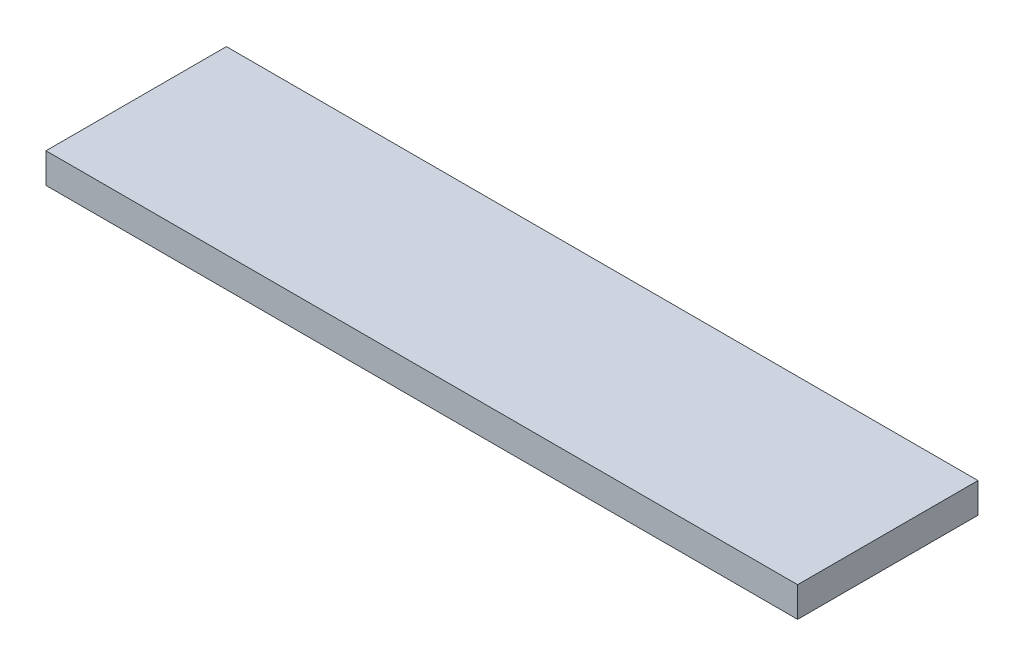
SolidWorks part; units mm, degrees
material "Natural Rubber"
ref_plane "Front" through (0, 0, 0) normal (0, 0, 1) x (1, 0, 0)
ref_plane "Top" through (0, 0, 0) normal (0, 1, 0) x (1, 0, 0)
ref_plane "Right" through (0, 0, 0) normal (1, 0, 0) x (0, 0, -1)
sketch "Sketch1" plane through (0, 0, 0) normal (0, 1, 0) x (1, 0, 0)
  line L1 (-1447.8, 825.5) -> (1447.8, 825.5)
  line L2 (-1447.8, 825.5) -> (-1447.8, -825.5)
  line L3 (-1447.8, -825.5) -> (1447.8, -825.5)
  line L4 (1447.8, 825.5) -> (1447.8, -825.5)
  line L5 (-1447.8, 825.5) -> (1447.8, -825.5) construction
  line L6 (-1447.8, -825.5) -> (1447.8, 825.5) construction
  point P0 (0, 0)
  dimension "D1" = 2895.6
  dimension "D2" = 1651
extrude "Boss-Extrude1" [suppressed] add sketch "Sketch1" along normal blind 1473.2
sketch "Sketch2" [suppressed] plane through (0, 0, 0) normal (0, -1, 0) x (1, 0, 0)
  line L0 (0, 0) -> (2162.175, 0) construction
  line L1 (1447.8, 825.5) -> (1447.8, -825.5) construction
  line L2 (1752.6, 663.575) -> (2571.75, 663.575)
  line L3 (1752.6, 663.575) -> (1752.6, -663.575)
  line L4 (1752.6, -663.575) -> (2571.75, -663.575)
  line L5 (2571.75, 663.575) -> (2571.75, -663.575)
  line L6 (1752.6, 663.575) -> (2571.75, -663.575) construction
  line L7 (1752.6, -663.575) -> (2571.75, 663.575) construction
  dimension "D1" = 1327.15
  dimension "D2" = 819.15
  dimension "D3" = 304.8
extrude "Boss-Extrude2" [suppressed] add sketch "Sketch2" against normal blind 736.6 separate body
sketch "Sketch3" plane through (0, 0, 0) normal (0, 1, 0) x (-1, 0, 0)
  line L2 (3810, 914.4) -> (-3810, 914.4)
  line L3 (3810, 914.4) -> (3810, -914.4)
  line L4 (3810, -914.4) -> (-3810, -914.4)
  line L5 (-3810, 914.4) -> (-3810, -914.4)
  line L6 (3810, 914.4) -> (-3810, -914.4) construction
  line L7 (3810, -914.4) -> (-3810, 914.4) construction
  dimension "D1" = 1828.8
  dimension "D2" = 7620
  dimension "D4" = 1828.8
  dimension "D5" = 7620
extrude "Boss-Extrude3" add sketch "Sketch3" along normal blind 304.8 separate body
